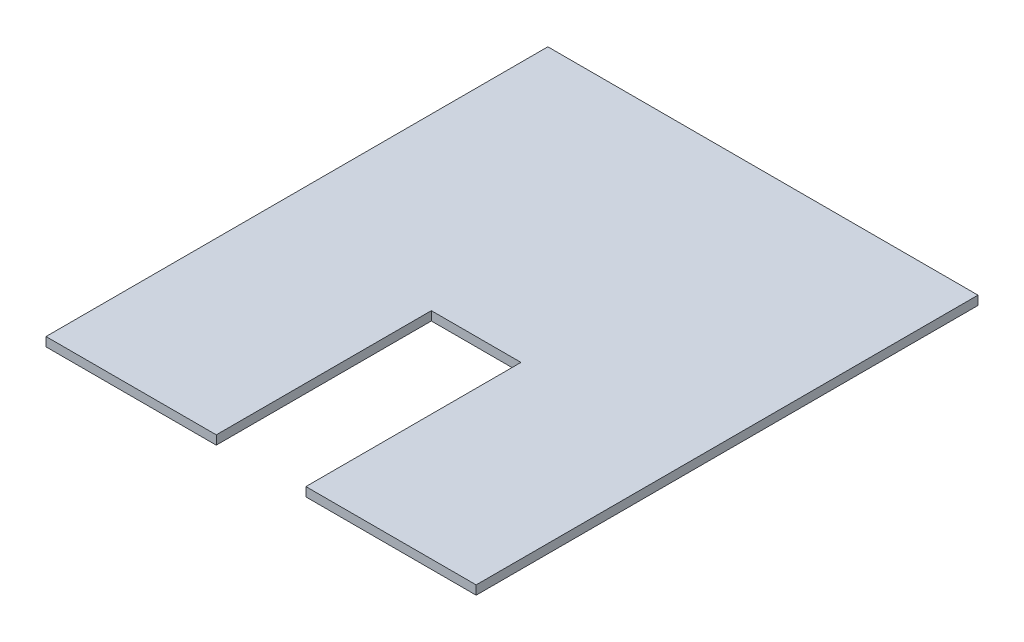
SolidWorks part; units mm, degrees
ref_plane "Front Plane" through (0, 0, 0) normal (0, 0, 1) x (1, 0, 0)
ref_plane "Top Plane" through (0, 0, 0) normal (0, 1, 0) x (1, 0, 0)
ref_plane "Right Plane" through (0, 0, 0) normal (1, 0, 0) x (0, 0, -1)
sketch "Sketch1" plane through (0, 0, 0) normal (0, 1, 0) x (1, 0, 0)
  line L1 (-152.4, -177.8) -> (152.4, -177.8)
  line L2 (-152.4, -177.8) -> (-152.4, 177.8)
  line L3 (-152.4, 177.8) -> (152.4, 177.8)
  line L4 (152.4, -177.8) -> (152.4, 177.8)
  line L5 (-152.4, -177.8) -> (152.4, 177.8) construction
  line L6 (-152.4, 177.8) -> (152.4, -177.8) construction
  point P0 (0, 0)
  dimension "D1" = 355.6
  dimension "D2" = 304.8
extrude "Boss-Extrude1" add sketch "Sketch1" along normal blind 6.35
sketch "Sketch2" plane through (0, 6.35, 0) normal (0, 1, 0) x (1, 0, 0)
  line L0 (-152.4, -177.8) -> (152.4, -177.8) construction
  line L1 (-31.75, -25.4) -> (31.75, -25.4)
  line L2 (-31.75, -25.4) -> (-31.75, -177.8)
  line L3 (-31.75, -177.8) -> (31.75, -177.8)
  line L4 (31.75, -25.4) -> (31.75, -177.8)
  line L5 (-31.75, -25.4) -> (31.75, -177.8) construction
  line L6 (-31.75, -177.8) -> (31.75, -25.4) construction
  point P0 (0, -101.6)
  dimension "D1" = 152.4
  dimension "D2" = 63.5
extrude "Cut-Extrude1" cut sketch "Sketch2" against normal through all
